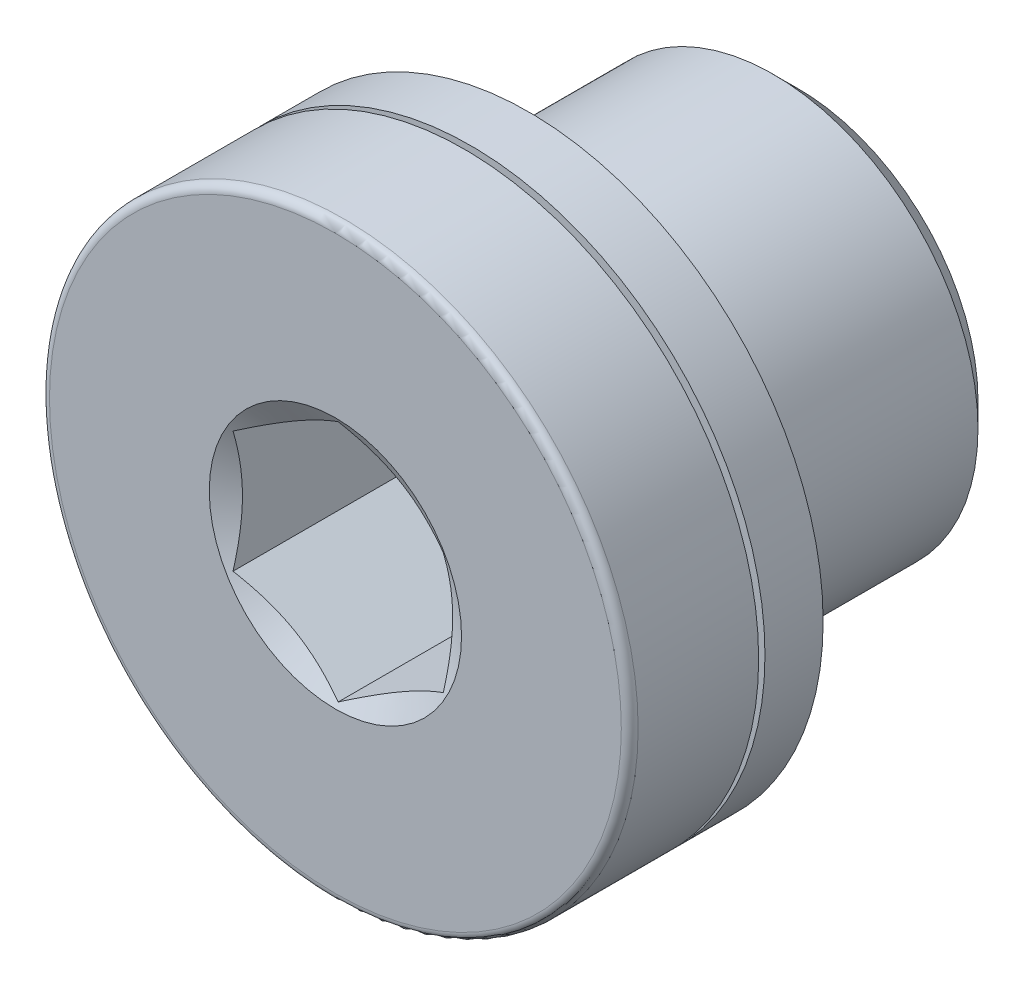
SolidWorks part; units mm, degrees
ref_plane "Ebene vorne" through (0, 0, 0) normal (0, 0, 1) x (1, 0, 0)
ref_plane "Ebene oben" through (0, 0, 0) normal (0, 1, 0) x (1, 0, 0)
ref_plane "Ebene rechts" through (0, 0, 0) normal (1, 0, 0) x (0, 0, -1)
sketch "Skizze1" plane through (0, 0, 0) normal (1, 0, 0) x (0, 0, -1)
  line L0 (-2.8679, 0) -> (-4.6, 3)
  line L1 (-4.6, 3) -> (-4.6, 6.8)
  line L2 (-4.4, 7) -> (-1.5333, 7)
  line L3 (-1.5333, 7) -> (-1.5333, 6.3)
  line L4 (-1.5333, 6.3) -> (-1.3833, 6.3)
  line L5 (-1.3833, 6.3) -> (-1.3833, 7)
  line L6 (-1.3833, 7) -> (0, 7)
  line L7 (0, 7) -> (0, 4.283)
  line L8 (0, 4.283) -> (0.581, 4.864)
  line L9 (0.581, 4.864) -> (5.819, 4.864)
  line L10 (5.819, 4.864) -> (6.4, 4.283)
  line L11 (6.4, 4.283) -> (6.4, 0)
  line L12 (6.4, 0) -> (-2.8679, 0)
  line L13 (6.4, 0) -> (-2.8679, 0) construction
  arc A0 (-4.6, 6.8) -> (-4.4, 7) centre (-4.4, 6.8) cw
revolve "Rotation1" add sketch "Skizze1" angle 360 about L13 reverse direction yes
cosmetic thread "Gewindedarstellung1" parameters "D1"=6.4, "D2"=8.566
ref_plane "Ebene1" through (0, 0, 4.6) normal (0, 0, 1) x (1, 0, 0)
sketch "Skizze2" plane through (0, 0, 4.6) normal (0, 0, 1) x (1, 0, 0)
  line L0 (-2.5, -1.4434) -> (0, -2.8868)
  line L1 (0, -2.8868) -> (2.5, -1.4434)
  line L2 (2.5, -1.4434) -> (2.5, 1.4434)
  line L3 (2.5, 1.4434) -> (0, 2.8868)
  line L4 (0, 2.8868) -> (-2.5, 1.4434)
  line L5 (-2.5, 1.4434) -> (-2.5, -1.4434)
extrude "Schnitt-Linear austragen1" cut sketch "Skizze2" against normal blind 4.6
ref_plane "ANBAU XY" through (0, 0, 0) normal (0, 0, 1) x (1, 0, 0)
ref_plane "ANBAU XZ" through (0, 0, 0) normal (0, -1, 0) x (-1, 0, 0)
ref_plane "ANBAU YZ" through (0, 0, 0) normal (1, 0, 0) x (0, 0, -1)
ref_axis "ANBAU X" through (-80.9, 0, 0) along (1, 0, 0)
ref_axis "ANBAU Y" through (0, -50, 0) along (0, 1, 0)
ref_axis "ANBAU Z" through (0, 0, 80.9) along (0, 0, -1)
sketch3d "ANBAU"
  point P0 (0, 0, 0)
ref_plane "ANBAU_STD XY" through (0, 0, 0) normal (0, 0, 1) x (1, 0, 0)
ref_plane "ANBAU_STD XZ" through (0, 0, 0) normal (0, -1, 0) x (-1, 0, 0)
ref_plane "ANBAU_STD YZ" through (0, 0, 0) normal (1, 0, 0) x (0, 0, -1)
ref_axis "ANBAU_STD X" through (-80.9, 0, 0) along (1, 0, 0)
ref_axis "ANBAU_STD Y" through (0, -50, 0) along (0, 1, 0)
ref_axis "ANBAU_STD Z" through (0, 0, 80.9) along (0, 0, -1)
sketch3d "ANBAU_STD"
  point P0 (0, 0, 0)
